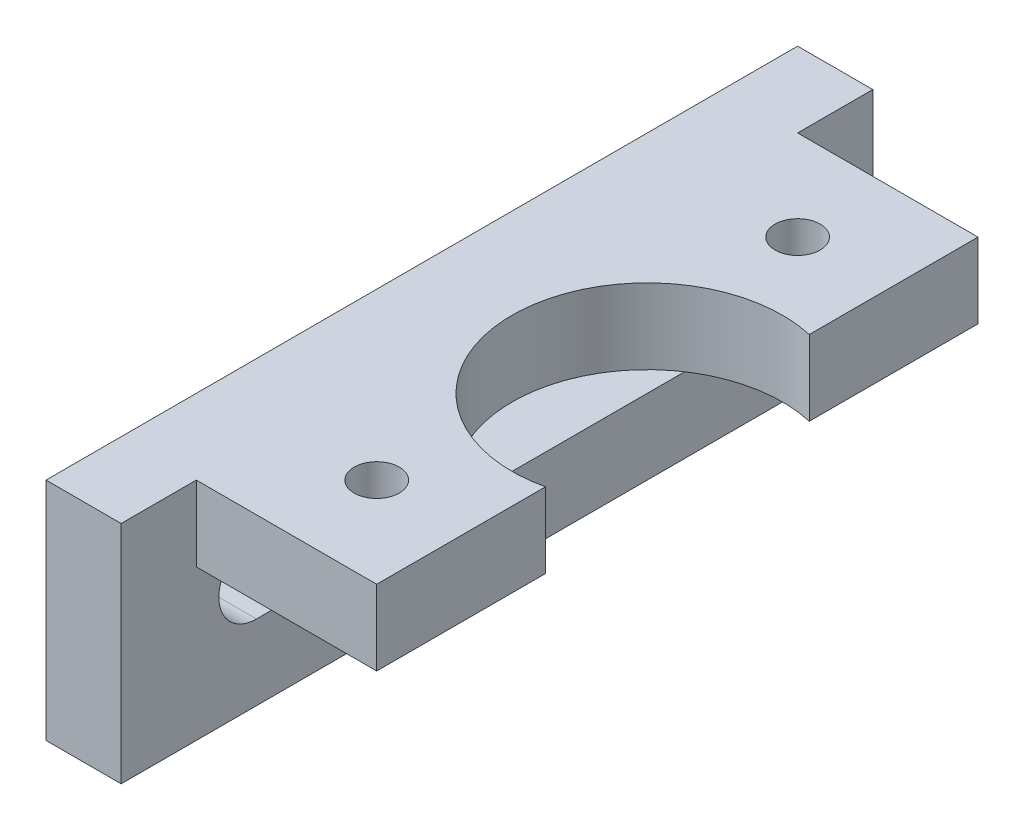
SolidWorks part; units mm, degrees
ref_plane "前视基准面" through (0, 0, 0) normal (0, 0, 1) x (1, 0, 0)
ref_plane "上视基准面" through (0, 0, 0) normal (0, 1, 0) x (1, 0, 0)
ref_plane "右视基准面" through (0, 0, 0) normal (1, 0, 0) x (0, 0, -1)
sketch "草图1" plane through (0, 0, 0) normal (-1, 0, 0) x (0, 0, 1)
  line L0 (-16, 0) -> (16, 0) construction
  line L1 (-25, 7.5) -> (25, 7.5)
  line L2 (-25, 7.5) -> (-25, -7.5)
  line L3 (-25, -7.5) -> (25, -7.5)
  line L4 (25, 7.5) -> (25, -7.5)
  line L5 (0, -7.5) -> (0, 7.5) construction
  line L6 (-25, 0) -> (25, 0) construction
  line L7 (-16, 2.5) -> (16, 2.5)
  line L8 (-16, -2.5) -> (16, -2.5)
  arc A0 (-16, 2.5) -> (-16, -2.5) centre (-16, 0) ccw
  arc A1 (16, -2.5) -> (16, 2.5) centre (16, 0) ccw
  point P0 (0, 0)
  point P6 (0, 0)
  dimension "D2" = 2.5
  dimension "D1" = 32
  dimension "D3" = 15
  dimension "D4" = 50
extrude "凸台-拉伸1" add sketch "草图1" along normal blind 5
sketch "草图2" plane through (0, 0, 0) normal (1, 0, 0) x (0, 0, -1)
  line L0 (44.9748, 0) -> (-44.7797, 0) construction
  line L1 (-25, 7.5) -> (25, 7.5) construction
  line L3 (-20, 7.5) -> (20, 7.5)
  line L4 (-20, 7.5) -> (-20, 2.5)
  line L5 (-20, 2.5) -> (20, 2.5)
  line L6 (20, 7.5) -> (20, 2.5)
  line L7 (0, 0) -> (0, 16.4675) construction
  line L13 (-16, 2.5) -> (16, 2.5) construction
  dimension "D1" = 40
extrude "凸台-拉伸3" add sketch "草图2" along normal blind 12
sketch "草图3" plane through (0, 7.5, 0) normal (0, 1, 0) x (1, 0, 0)
  line L0 (-5, -25) -> (-5, 25) construction
  line L1 (12, 20) -> (0, 20) construction
  line L2 (12, -20) -> (0, -20) construction
  line L3 (12, 20) -> (12, -20) construction
  circle A1 centre (10, 0) radius 9
  circle A2 centre (6, 14) radius 1.5
  circle A3 centre (6, -14) radius 1.5
  point P10 (0, 0)
  dimension "D1" = 6
  dimension "D3" = 3
  dimension "D6" = 18
  dimension "D2" = 6
  dimension "D4" = 6
  dimension "D5" = 15
extrude "切除-拉伸1" cut sketch "草图3" against normal through all
